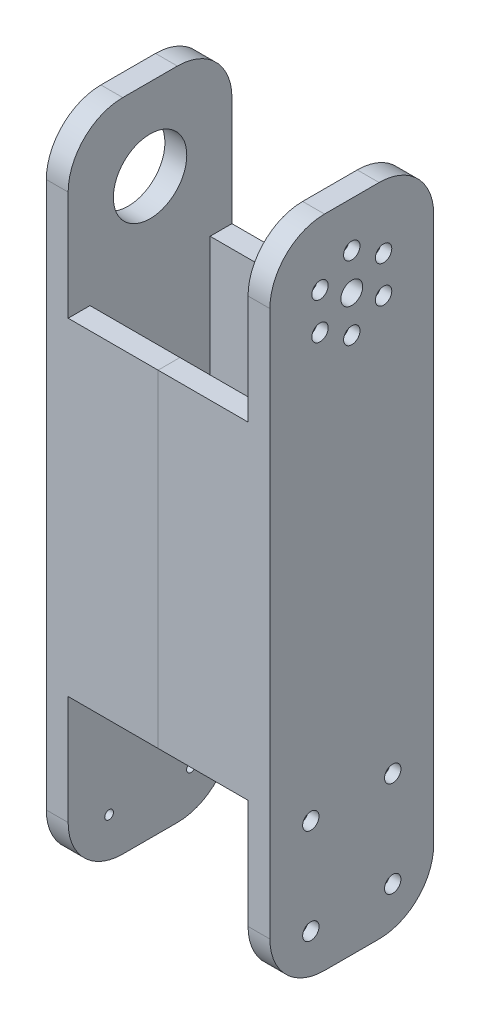
SolidWorks part; units mm, degrees
ref_plane "前视基准面" through (0, 0, 0) normal (0, 0, 1) x (1, 0, 0)
ref_plane "上视基准面" through (0, 0, 0) normal (0, 1, 0) x (1, 0, 0)
ref_plane "右视基准面" through (0, 0, 0) normal (1, 0, 0) x (0, 0, -1)
other "Configuration Table"
sketch "草图1" plane through (0, 0, 0) normal (1, 0, 0) x (0, 0, -1)
  line L1 (30, -120) -> (-30, -120)
  line L2 (30, -120) -> (30, 120)
  line L3 (30, 120) -> (-30, 120)
  line L4 (-30, -120) -> (-30, 120)
  line L5 (30, -120) -> (-30, 120) construction
  line L6 (30, 120) -> (-30, -120) construction
  point P0 (0, 0)
  dimension "D1" = 240
  dimension "D2" = 60
extrude "凸台-拉伸1" add sketch "草图1" along normal blind 8
sketch "草图2" plane through (8, 0, 0) normal (1, 0, 0) x (0, 0, -1)
  line L1 (30, 120) -> (-30, 120) construction
  circle A12 centre (0, 90) radius 13.45
  point P6 (0, 120)
  point P26 (0, 90)
  dimension "D11" = 26.9
  dimension "D2" = 30
extrude "切除-拉伸1" cut sketch "草图2" against normal through all
sketch "草图3" plane through (8, 0, 0) normal (1, 0, 0) x (0, 0, -1)
  line L0 (-30, 120) -> (-30, -120) construction
  line L1 (-22, -60) -> (-30, -60)
  line L2 (-22, -60) -> (-22, 60)
  line L3 (-22, 60) -> (-30, 60)
  line L4 (-30, -60) -> (-30, 60)
  line L5 (-22, -60) -> (-30, 60) construction
  line L6 (-22, 60) -> (-30, -60) construction
  line L7 (30, -60) -> (22, -60)
  line L8 (30, -60) -> (30, 60)
  line L9 (30, 60) -> (22, 60)
  line L10 (22, -60) -> (22, 60)
  line L11 (30, -60) -> (22, 60) construction
  line L12 (30, 60) -> (22, -60) construction
  line L13 (30, -120) -> (30, 120) construction
  line L14 (30, 120) -> (-30, 120) construction
  line L15 (-30, -120) -> (30, -120) construction
  point P0 (-26, 0)
  point P5 (26, 0)
  dimension "D1" = 60
  dimension "D2" = 60
  dimension "D3" = 60
  dimension "D4" = 60
  dimension "D5" = 8
  dimension "D6" = 8
extrude "凸台-拉伸2" add sketch "草图3" along normal blind 65.9
sketch "草图4" plane through (73.9, 0, 0) normal (1, 0, 0) x (0, 0, -1)
  line L0 (30, -120) -> (-30, 120) construction
  line L1 (30, -120) -> (-30, -120)
  line L2 (30, -120) -> (30, 120)
  line L3 (30, 120) -> (-30, 120)
  line L4 (-30, -120) -> (-30, 120)
  line L5 (30, -120) -> (-30, 120) construction
  line L6 (30, 120) -> (-30, -120) construction
  line L7 (30, 120) -> (-30, 120) construction
  point P0 (0, 0)
extrude "凸台-拉伸3" add sketch "草图4" along normal blind 8
fillet "圆角1" radius 20 8 edges at (4, -120, 30) (4, -120, -30) (4, 120, -30) (4, 120, 30) (77.9, 120, -30) (77.9, 120, 30) (77.9, -120, -30) (77.9, -120, 30)
sketch "草图9" plane through (73.9, 0, 0) normal (-1, 0, 0) x (0, 0, 1)
  circle A0 centre (0, 90) radius 19 construction
  circle A2 centre (0, 109) radius 1.6
  circle A3 centre (19, 90) radius 1.6
  circle A4 centre (0, 71) radius 1.6
  circle A5 centre (-19, 90) radius 1.6
  point P14 (0, 90)
  dimension "D1" = 38
  dimension "D2" = 3.2
sketch "草图10" plane through (81.9, 0, 0) normal (1, 0, 0) x (0, 0, -1)
  circle A0 centre (0, 90) radius 4
  circle A1 centre (0, 90) radius 13.5 construction
  circle A2 centre (0, 103.5) radius 1.6
  circle A3 centre (11.6913, 96.75) radius 1.6
  circle A4 centre (11.6913, 83.25) radius 1.6
  circle A5 centre (0, 76.5) radius 1.6
  circle A6 centre (-11.6913, 83.25) radius 1.6
  circle A7 centre (-11.6913, 96.75) radius 1.6
  point P18 (0, 90)
  dimension "D1" = 8
  dimension "D2" = 27
  dimension "D3" = 3.2
  dimension "D4" = 6
extrude "切除-拉伸2" cut sketch "草图10" against normal up to next
sketch "草图15" plane through (73.9, 0, 0) normal (-1, 0, 0) x (0, 0, 1)
  circle A0 centre (0, 90) radius 18
  dimension "D1" = 36
extrude "凸台-拉伸4" add sketch "草图15" along normal blind 9.8
sketch "草图11" plane through (81.9, 0, 0) normal (1, 0, 0) x (0, 0, -1)
  line L1 (15, -105) -> (-15, -105) construction
  line L2 (15, -105) -> (15, -70) construction
  line L3 (15, -70) -> (-15, -70) construction
  line L4 (-15, -105) -> (-15, -70) construction
  line L5 (15, -105) -> (-15, -70) construction
  line L6 (15, -70) -> (-15, -105) construction
  line L7 (-30, 100) -> (-30, -100) construction
  line L8 (30, -100) -> (30, 100) construction
  line L9 (0, -70) -> (0, -105) construction
  line L10 (-15, -87.5) -> (15, -87.5) construction
  line L11 (-22, -60) -> (-30, -60) construction
  circle A0 centre (-15, -70) radius 1.6
  circle A1 centre (15, -70) radius 1.6
  circle A2 centre (15, -105) radius 1.6
  circle A3 centre (-15, -105) radius 1.6
  point P0 (0, -87.5)
  dimension "D5" = 3.2
  dimension "D1" = 10
  dimension "D2" = 15
  dimension "D3" = 15
  dimension "D4" = 35
extrude "切除-拉伸3" cut sketch "草图11" against normal through all
sketch "草图12" plane through (81.9, 0, 0) normal (1, 0, 0) x (0, 0, -1)
  circle A0 centre (0, 103.45) radius 3
  circle A1 centre (0, 90) radius 13.45 construction
  circle A2 centre (11.648, 96.725) radius 3
  circle A3 centre (11.648, 83.275) radius 3
  circle A4 centre (0, 76.55) radius 3
  circle A5 centre (-11.648, 83.275) radius 3
  circle A6 centre (-11.648, 96.725) radius 3
  point P16 (0, 90)
  dimension "D1" = 6
  dimension "D2" = 6
extrude "切除-拉伸4" cut sketch "草图12" against normal blind 4
sketch "草图13" plane through (81.9, 0, 0) normal (1, 0, 0) x (0, 0, -1)
  line L2 (0, -70) -> (0, -105) construction
  line L3 (-15, -87.5) -> (15, -87.5) construction
  circle A0 centre (-15, -70) radius 3
  circle A1 centre (15, -70) radius 3
  circle A2 centre (15, -105) radius 3
  circle A3 centre (-15, -105) radius 3
  dimension "D1" = 6
extrude "切除-拉伸5" cut sketch "草图13" against normal blind 4
sketch "草图14" plane through (0, 0, 0) normal (-1, 0, 0) x (0, 0, 1)
  line L0 (0, -70) -> (0, -105) construction
  line L1 (-15, -87.5) -> (15, -87.5) construction
  circle A0 centre (-15, -70) radius 3
  circle A1 centre (15, -70) radius 3
  circle A2 centre (15, -105) radius 3
  circle A3 centre (-15, -105) radius 3
  dimension "D1" = 6
extrude "切除-拉伸6" cut sketch "草图14" against normal blind 4
extrude "切除-拉伸7" cut sketch "草图10<2>" against normal up to next
sketch "草图10<2>" plane through (81.9, 0, 0) normal (1, 0, 0) x (0, 0, -1) same geometry as "草图10"
ref_plane "基准面1" through (40.95, 0, 0) normal (1, 0, 0) x (0, 0, -1)
split "分割1" trim tools "基准面1" bodies to split 124 resulting bodies 125 126
